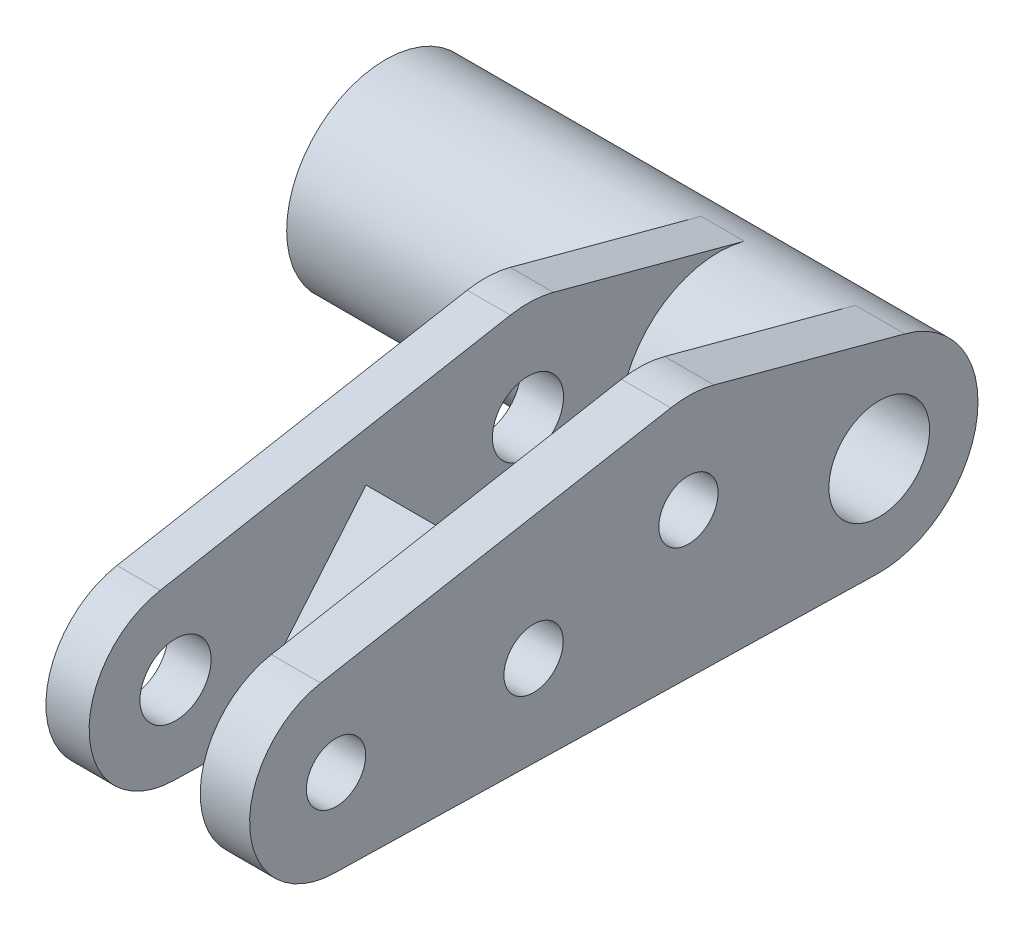
SolidWorks part; units mm, degrees
ref_plane "Front Plane" through (0, 0, 0) normal (0, 0, 1) x (1, 0, 0)
ref_plane "Top Plane" through (0, 0, 0) normal (0, 1, 0) x (1, 0, 0)
ref_plane "Right Plane" through (0, 0, 0) normal (1, 0, 0) x (0, 0, -1)
sketch "Sketch1" plane through (0, 0, 0) normal (1, 0, 0) x (0, 0, -1)
  line L0 (-0.1443, -6.3484) -> (-35.0513, -5.5548)
  line L1 (-35.9129, 5.4677) -> (-13.3962, 9.5358)
  line L2 (-10.6238, 9.4206) -> (1.6435, 6.1336)
  line L3 (-34.925, 0) -> (0, 0) construction
  line L4 (0, 0) -> (-12.2673, 3.287) construction
  arc A0 (-0.1443, -6.3484) -> (1.6435, 6.1336) centre (0, 0) ccw
  arc A1 (-35.0513, -5.5548) -> (-35.9129, 5.4677) centre (-34.925, 0) cw
  arc A2 (-13.3962, 9.5358) -> (-10.6238, 9.4206) centre (-12.2673, 3.287) cw
  dimension "D1" = 6.35
  dimension "D2" = 11.1125
  dimension "D3" = 34.925
  dimension "D4" = 12.7
  dimension "D5" = 15
extrude "Boss-Extrude1" add sketch "Sketch1" against normal blind 13.0969
sketch "Sketch6" plane through (0, 0, 0) normal (1, 0, 0) x (0, 0, -1)
  line L0 (1.6435, 6.1336) -> (-10.6238, 9.4206) construction
  line L1 (-13.3962, 9.5358) -> (-35.9129, 5.4677) construction
  line L2 (1.6435, 6.1336) -> (-10.6238, 9.4206)
  line L3 (-13.3962, 9.5358) -> (-35.9129, 5.4677)
  line L5 (-22.6776, 4.7171) -> (-30.0606, -4.0817)
  line L6 (-35.0513, -5.5548) -> (-0.1443, -6.3484) construction
  line L7 (-35.0513, -5.5548) -> (-31.9779, -5.6247)
  line L8 (-34.925, 0) -> (0, 0) construction
  line L9 (-16.7574, -1.2031) -> (-22.6776, 4.7171)
  arc A0 (-10.6238, 9.4206) -> (-13.3962, 9.5358) centre (-12.2673, 3.287) ccw construction
  arc A1 (-35.9129, 5.4677) -> (-35.0513, -5.5548) centre (-34.925, 0) ccw construction
  arc A2 (-10.6238, 9.4206) -> (-13.3962, 9.5358) centre (-12.2673, 3.287) ccw
  arc A3 (-35.9129, 5.4677) -> (-35.0513, -5.5548) centre (-34.925, 0) ccw
  arc A4 (1.6435, 6.1336) -> (-6.1336, 1.6435) centre (0, 0) ccw
  arc A5 (-6.1336, 1.6435) -> (-16.7574, -1.2031) centre (-12.2673, 3.287) cw
  arc A6 (-30.0606, -4.0817) -> (-31.9779, -5.6247) centre (-34.925, 0) cw
  dimension "D1" = 6.35
  dimension "D2" = 50
  dimension "D3" = 45
extrude "Cut-Extrude4" cut sketch "Sketch6" against normal blind 7.1437 from offset 3.175 offset against normal yes
sketch "Sketch3" plane through (0, 0, 0) normal (1, 0, 0) x (0, 0, -1)
  circle A0 centre (0, 0) radius 3.2385
  circle A1 centre (-34.925, 0) radius 1.905
  circle A2 centre (-12.2673, 3.287) radius 1.905
  circle A3 centre (-22.225, 0) radius 1.905
  circle A4 centre (-22.225, 0) radius 4.445 construction
  circle A5 centre (-34.925, 0) radius 4.445 construction
  dimension "D1" = 3.81
  dimension "D2" = 6.477
  dimension "D3" = 8.89
  dimension "D4" = 22.225
extrude "Cut-Extrude2" cut sketch "Sketch3" against normal through all
sketch "Sketch4" plane through (-13.0969, 0, 0) normal (-1, 0, 0) x (0, 0, 1)
  circle A0 centre (0, 0) radius 6.35
  circle A1 centre (0, 0) radius 3.2385
  circle A2 centre (0, 0) radius 3.2385 construction
  arc A3 (-1.6435, 6.1336) -> (0.1443, -6.3484) centre (0, 0) ccw construction
extrude "Boss-Extrude2" add sketch "Sketch4" along normal up to surface (18.6531 mm away)
sketch "Sketch5" plane through (-13.0969, 0, 0) normal (-1, 0, 0) x (0, 0, 1)
  circle A0 centre (12.2673, 3.287) radius 2.286
  circle A1 centre (22.225, 0) radius 2.286
  circle A2 centre (34.925, 0) radius 2.286
  dimension "D1" = 4.572
extrude "Cut-Extrude5" cut sketch "Sketch5" against normal up to surface (2.7781 mm away) up to face at (-10.3187, 3.287, 10.3623)
